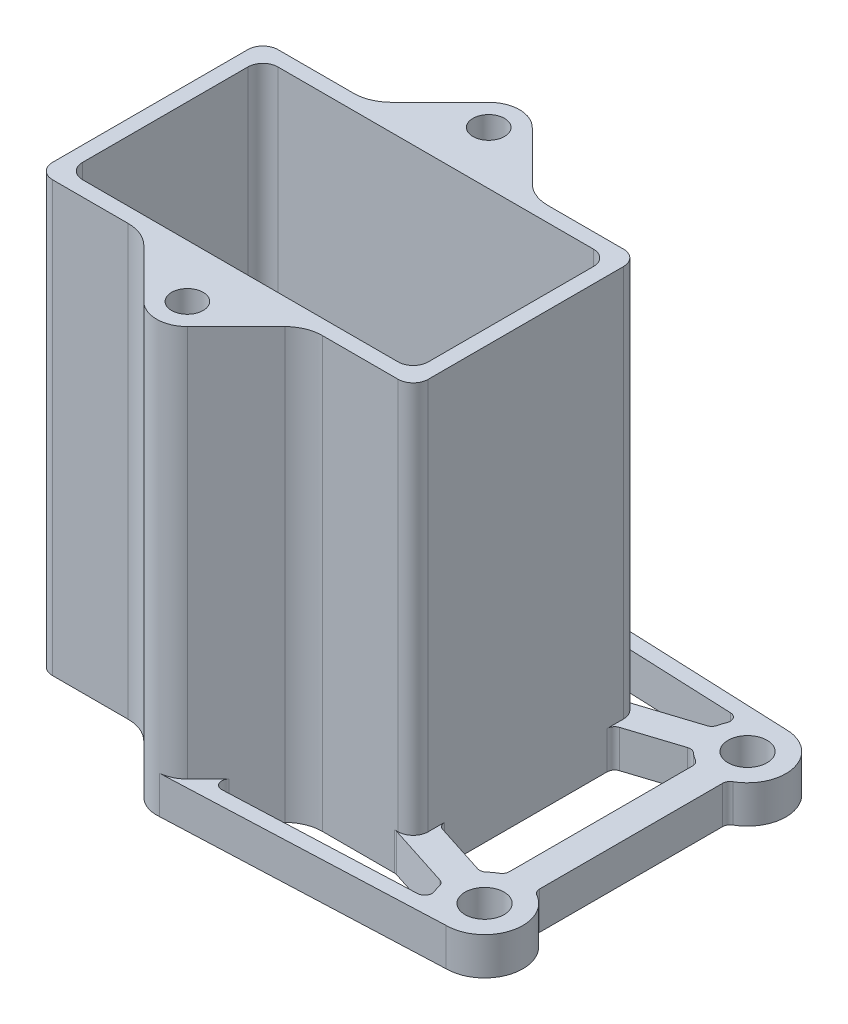
SolidWorks part; units mm, degrees
ref_plane "Front Plane" through (0, 0, 0) normal (0, 0, 1) x (1, 0, 0)
ref_plane "Top Plane" through (0, 0, 0) normal (0, 1, 0) x (1, 0, 0)
ref_plane "Right Plane" through (0, 0, 0) normal (1, 0, 0) x (0, 0, -1)
sketch "Sketch1" plane through (0, 0, 0) normal (0, 1, 0) x (1, 0, 0)
  line L1 (-25, -15) -> (25, -15)
  line L2 (-25, -15) -> (-25, 15)
  line L3 (-25, 15) -> (25, 15)
  line L4 (25, -15) -> (25, 15)
  line L5 (-25, -15) -> (25, 15) construction
  line L6 (-25, 15) -> (25, -15) construction
  point P0 (0, 0)
  dimension "D1" = 30
  dimension "D2" = 50
extrude "Boss-Extrude1" add sketch "Sketch1" along normal blind 3
sketch "Sketch2" plane through (0, 3, 0) normal (0, 1, 0) x (1, 0, 0)
  line L0 (23, -13) -> (23, 13)
  line L1 (23, 13) -> (-23, 13)
  line L2 (-23, 13) -> (-23, -13)
  line L3 (-23, -13) -> (23, -13)
  line L4 (25, -15) -> (25, 15)
  line L5 (25, 15) -> (-25, 15)
  line L6 (-25, 15) -> (-25, -15)
  line L7 (-25, -15) -> (25, -15)
  line L8 (25, -15) -> (25, 15)
  line L9 (25, 15) -> (-25, 15)
  line L10 (-25, 15) -> (-25, -15)
  line L11 (-25, -15) -> (25, -15)
  dimension "D1" = 0
  dimension "D2" = 2
extrude "Boss-Extrude2" add sketch "Sketch2" along normal blind 54.15
sketch "Sketch3" plane through (0, 0, 0) normal (0, 1, 0) x (1, 0, 0)
  line L0 (0, 0) -> (0, 20.05) construction
  line L1 (-2.8991, 22.9491) -> (-10.8483, 15)
  line L2 (-10.8483, 15) -> (10.8483, 15)
  line L3 (10.8483, 15) -> (2.8991, 22.9491)
  line L4 (25, -15) -> (25, 15)
  line L5 (-25, -15) -> (25, -15)
  line L6 (-25, 15) -> (-25, -15)
  line L7 (25, 15) -> (-25, 15)
  line L8 (25, -15) -> (25, 15)
  line L9 (-25, -15) -> (25, -15)
  line L10 (-25, 15) -> (-25, -15)
  line L11 (25, 15) -> (-25, 15)
  arc A0 (2.8991, 22.9491) -> (-2.8991, 22.9491) centre (0, 20.05) ccw
  circle A1 centre (0, 20.05) radius 2.1
  dimension "D3" = 2
  dimension "D4" = 4.2
  dimension "D2" = 45
  dimension "D5" = 20.05
  dimension "D1" = 0
extrude "Boss-Extrude3" add sketch "Sketch3" along direction (0, -1, 0) on the side of the normal up to surface (57.15 mm away) contours L3 A0 L1 L2 A1 L11 region at (0, 0, -23.9145) up to face at (0, 57.15, 0)
mirror "Mirror1" about plane through (0, 0, 0) normal (0, 0, 1) of "Boss-Extrude3"
fillet "Fillet1" radius 2 8 edges at (-25, 28.575, 15) (-23, 30.075, 13) (23, 30.075, 13) (25, 28.575, 15) (23, 30.075, -13) (25, 28.575, -15) (-23, 30.075, -13) (-25, 28.575, -15)
sketch "Sketch4" plane through (-25, 0, 0) normal (-1, 0, 0) x (0, 0, 1)
  circle A0 centre (0, 12.7) radius 5
  point P2 (0, 0)
  dimension "D2" = 10
  dimension "D1" = 12.7
extrude "Cut-Extrude1" cut sketch "Sketch4" against normal up to surface (2 mm away) up to face at (-23, 30.075, 0)
sketch "Sketch5" plane through (0, 0, 0) normal (0, 1, 0) x (1, 0, 0)
  line L0 (0, 0) -> (37, 0) construction
  line L1 (37, 0) -> (37, 17.5) construction
  line L2 (37, 22.6) -> (0, 24.15)
  line L3 (39, -12.8085) -> (39, 12.8085)
  line L4 (37, -22.6) -> (0, -24.15)
  line L5 (3.8618, 21.9865) -> (33.08, 20.7625)
  line L6 (3.8618, -21.9865) -> (33.08, -20.7625)
  line L7 (35, -12.8085) -> (35, 12.8085)
  line L8 (23, 13) -> (37, 17.5) construction
  line L9 (23, -13) -> (37, -17.5) construction
  line L10 (22.6865, 15) -> (31.9216, 17.9684)
  line L11 (25, 11.5421) -> (33.1456, 14.1603)
  line L12 (25, -11.5421) -> (33.1456, -14.1603)
  line L13 (22.6865, -15) -> (31.9216, -17.9684)
  line L15 (-23, -15) -> (-10.8483, -15)
  line L16 (-25, 13) -> (-25, -13)
  line L17 (-10.8483, 15) -> (-23, 15)
  line L18 (-2.8991, 22.9491) -> (-10.8483, 15)
  line L19 (10.8483, 15) -> (2.8991, 22.9491)
  line L20 (23, 15) -> (10.8483, 15)
  line L21 (25, -13) -> (25, 13)
  line L22 (10.8483, -15) -> (23, -15)
  line L23 (2.8991, -22.9491) -> (10.8483, -15)
  line L24 (-10.8483, -15) -> (-2.8991, -22.9491)
  line L25 (-23, -15) -> (-10.8483, -15)
  line L26 (-25, 13) -> (-25, -13)
  line L27 (-10.8483, 15) -> (-23, 15)
  line L28 (-2.8991, 22.9491) -> (-10.8483, 15)
  line L29 (10.8483, 15) -> (2.8991, 22.9491)
  line L30 (23, 15) -> (10.8483, 15)
  line L31 (25, -13) -> (25, 13)
  line L32 (10.8483, -15) -> (23, -15)
  line L33 (2.8991, -22.9491) -> (10.8483, -15)
  line L34 (-10.8483, -15) -> (-2.8991, -22.9491)
  circle A0 centre (37, 17.5) radius 2.6
  circle A1 centre (37, -17.5) radius 2.6
  circle A2 centre (37, 17.5) radius 5.1
  circle A3 centre (37, -17.5) radius 5.1
  arc A4 (2.8991, 22.9491) -> (-2.8991, 22.9491) centre (0, 20.05) ccw construction
  arc A5 (-2.8991, -22.9491) -> (2.8991, -22.9491) centre (0, -20.05) ccw construction
  arc A12 (-25, -13) -> (-23, -15) centre (-23, -13) ccw
  arc A13 (-23, 15) -> (-25, 13) centre (-23, 13) ccw
  arc A14 (2.8991, 22.9491) -> (-2.8991, 22.9491) centre (0, 20.05) ccw
  arc A15 (25, 13) -> (23, 15) centre (23, 13) ccw
  arc A16 (23, -15) -> (25, -13) centre (23, -13) ccw
  arc A17 (-2.8991, -22.9491) -> (2.8991, -22.9491) centre (0, -20.05) ccw
  arc A18 (-25, -13) -> (-23, -15) centre (-23, -13) ccw
  arc A19 (-23, 15) -> (-25, 13) centre (-23, 13) ccw
  arc A20 (2.8991, 22.9491) -> (-2.8991, 22.9491) centre (0, 20.05) ccw
  arc A21 (25, 13) -> (23, 15) centre (23, 13) ccw
  arc A22 (23, -15) -> (25, -13) centre (23, -13) ccw
  arc A23 (-2.8991, -22.9491) -> (2.8991, -22.9491) centre (0, -20.05) ccw
  point P51 (0, 0)
  dimension "D2" = 5.2
  dimension "D3" = 2.5
  dimension "D1" = 35
  dimension "D4" = 12
  dimension "D6" = 2
  dimension "D7" = 4
  dimension "D8" = 4
  dimension "D5" = 0
extrude "Boss-Extrude4" add sketch "Sketch5" along normal blind 5 contours A20 L29 L5 A2 L2 | A21 L31 L11 A2 L10 L30 | A2 L2 A0 | A3 L3 A2 L7 | A22 L32 L13 A3 L12 L31 | L4 A3 A1 | A23 L4 A3 L6 L33 region at (18.5063, 0, -22.4054) region at (40.5042, 0, -21.0042) region at (37, 0, 0) region at (28.419, 0, -14.7634) region at (41.1346, 0, 14.7679) region at (18.5063, 0, 22.4054) region at (28.419, 0, 14.7634)
fillet "Fillet2" radius 1 16 edges at (35, 2.5, -12.8085) (33.1456, 2.5, -14.1603) (22.6865, 2.5, 15) (33.08, 2.5, 20.7625) (31.9216, 2.5, 17.9684) (35, 2.5, 12.8085) (33.1456, 2.5, 14.1603) (3.8618, 2.5, 21.9865) (3.8618, 2.5, -21.9865) (31.9216, 2.5, -17.9684) (33.08, 2.5, -20.7625) (22.6865, 2.5, -15) (25, 2.5, -11.5421) (25, 2.5, 11.5421) (39, 2.5, 12.8085) (39, 2.5, -12.8085)
fillet "Fillet3" radius 5 4 edges at (10.8483, 28.575, 15) (-10.8483, 28.575, 15) (-10.8483, 28.575, -15) (10.8483, 28.575, -15)
